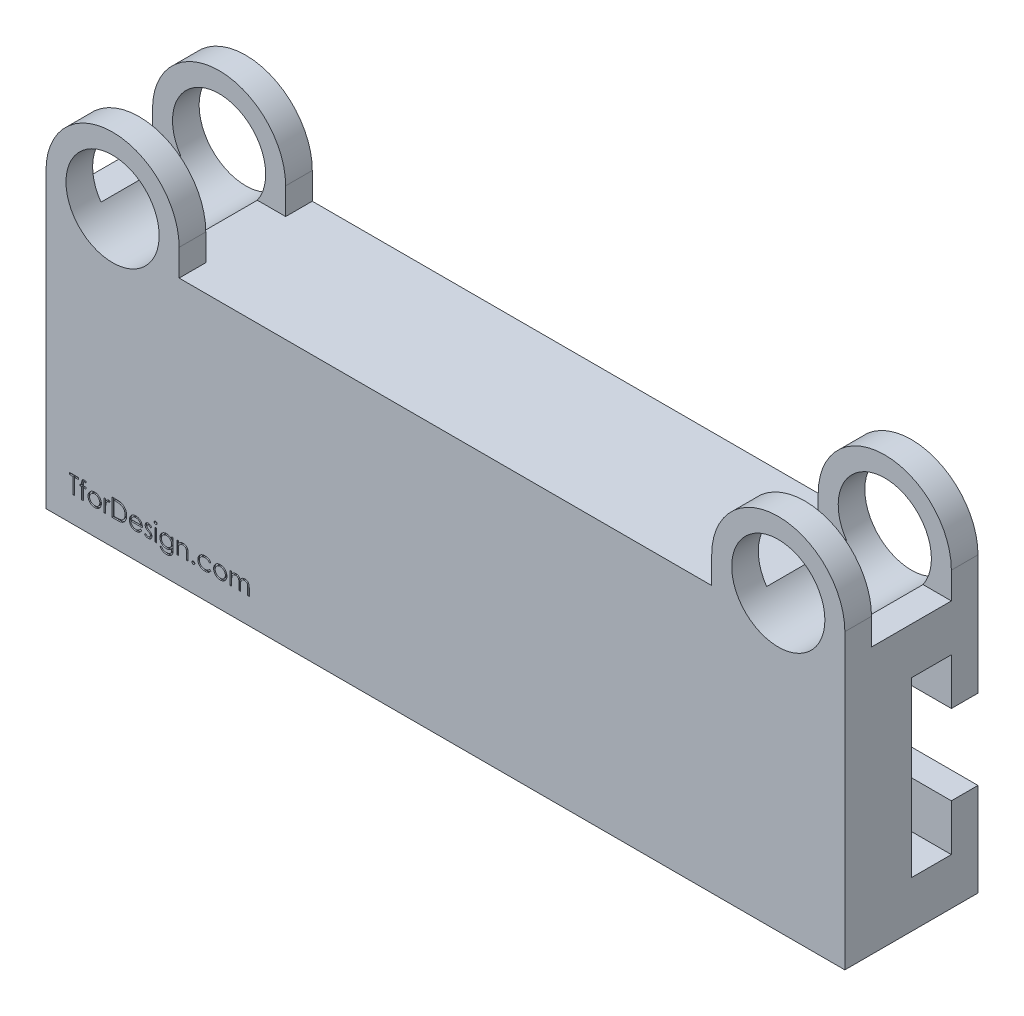
SolidWorks part; units mm, degrees
ref_plane "Front Plane" through (0, 0, 0) normal (0, 0, 1) x (1, 0, 0)
ref_plane "Top Plane" through (0, 0, 0) normal (0, 1, 0) x (1, 0, 0)
ref_plane "Right Plane" through (0, 0, 0) normal (1, 0, 0) x (0, 0, -1)
sketch "Sketch1" plane through (0, 0, 0) normal (0, 0, 1) x (1, 0, 0)
  line L1 (30, 10) -> (-30, 10)
  line L2 (30, 10) -> (30, -10)
  line L3 (30, -10) -> (-30, -10)
  line L4 (-30, 10) -> (-30, -10)
  line L5 (30, 10) -> (-30, -10) construction
  line L6 (30, -10) -> (-30, 10) construction
  point P0 (0, 0)
  dimension "D1" = 20
  dimension "D2" = 60
extrude "Boss-Extrude1" add sketch "Sketch1" along normal blind 10
sketch "Sketch2" plane through (0, 0, 10) normal (0, 0, 1) x (1, 0, 0)
  line L1 (30, 10) -> (20, 10)
  line L2 (30, 10) -> (30, 12)
  line L3 (30, 12) -> (20, 12)
  line L4 (20, 10) -> (20, 12)
  arc A0 (20, 12) -> (30, 12) centre (25, 12) cw
  line M6 (30, 10) -> (-30, 10)
  dimension "D1" = 10
  dimension "D2" = 2
extrude "Boss-Extrude2" add sketch "Sketch2" against normal up to surface (10 mm away) contours L4 L2 L3 M6 | A0 L3 region at (25, 11, 10) region at (25, 14.1221, 10) up to face at (0, 0, 0)
sketch "Sketch3" plane through (0, 0, 10) normal (0, 0, 1) x (1, 0, 0)
  circle A0 centre (25, 12) radius 3.5
  arc A1 (30, 12) -> (20, 12) centre (25, 12) ccw construction
  dimension "D1" = 7
extrude "Cut-Extrude1" cut sketch "Sketch3" against normal through all
mirror "Mirror1" about plane through (0, 0, 0) normal (1, 0, 0) of "Cut-Extrude1", "Boss-Extrude2"
sketch "Sketch4" plane through (-30, 0, 0) normal (-1, 0, 0) x (0, 0, 1)
  line L0 (10, 12) -> (10, -10) construction
  line L1 (2, 10) -> (8, 10)
  line L2 (2, 10) -> (2, 19.4201)
  line L3 (2, 19.4201) -> (8, 19.4201)
  line L4 (8, 10) -> (8, 19.4201)
  line L5 (2, 10) -> (0, 10) construction
  line L6 (0, 12) -> (0, -10) construction
  line L7 (8, 10) -> (10, 10) construction
  line L8 (0, 10) -> (10, 10) construction
  dimension "D1" = 2
extrude "Cut-Extrude2" cut sketch "Sketch4" against normal through all
sketch "Sketch5" plane through (0, 0, 0) normal (1, 0, 0) x (0, 0, -1)
  line L0 (0, -10) -> (0, 12) construction
  line L1 (-5, -6.5) -> (-2, -6.5)
  line L2 (-5, -6.5) -> (-5, 6.5)
  line L3 (-5, 6.5) -> (-2, 6.5)
  line L4 (-2, -6.5) -> (-2, 6.5)
  line L5 (-5, -6.5) -> (-2, 6.5) construction
  line L6 (-5, 6.5) -> (-2, -6.5) construction
  line L7 (-2, -3) -> (1.0411, -3)
  line L8 (-2, -3) -> (-2, 3)
  line L9 (-2, 3) -> (1.0411, 3)
  line L10 (1.0411, -3) -> (1.0411, 3)
  line L11 (-2, -3) -> (1.0411, 3) construction
  line L12 (-2, 3) -> (1.0411, -3) construction
  point P0 (-3.5, 0)
  point P5 (-0.4794, 0)
  dimension "D1" = 6
  dimension "D2" = 13
  dimension "D3" = 2
  dimension "D4" = 3
extrude "Cut-Extrude3" cut sketch "Sketch5" against normal through all both and the other way through all contours L1 L4 L3 L2 | L7 L10 L9 L4 region at (0, 0, 3.5) region at (0, 0, 0.4794)
sketch "Sketch6" plane through (0, 0, 10) normal (0, 0, 1) x (1, 0, 0)
  text T0 "TforDesign.com" font "Century Gothic" height in points 5
extrude "Cut-Extrude4" cut sketch "Sketch6" against normal blind 0.1
equation "\"D2@Sketch1\"=\"D1@Sketch1\"+40"
